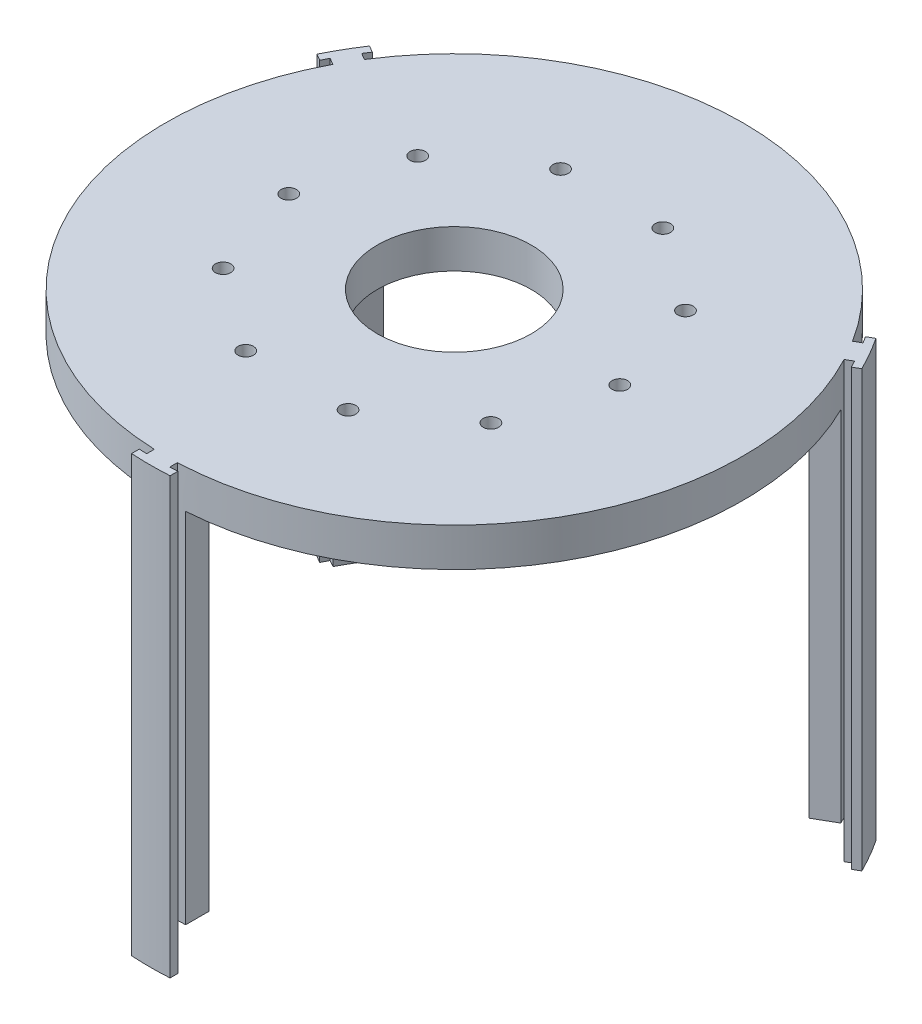
SolidWorks part; units mm, degrees
ref_plane "Front Plane" through (0, 0, 0) normal (0, 0, 1) x (1, 0, 0)
ref_plane "Top Plane" through (0, 0, 0) normal (0, 1, 0) x (1, 0, 0)
ref_plane "Right Plane" through (0, 0, 0) normal (1, 0, 0) x (0, 0, -1)
sketch "Sketch1" plane through (0, 0, 0) normal (0, 1, 0) x (1, 0, 0)
  circle A0 centre (0, 0) radius 37.5
  dimension "D1" = 75
extrude "Boss-Extrude1" add sketch "Sketch1" against normal blind 5
sketch "Sketch2" plane through (0, 0, 0) normal (0, 1, 0) x (1, 0, 0)
  line L0 (-2.75, 0) -> (2.75, 0) construction
  line L1 (0, 39.8902) -> (0, -39.5701) construction
  line L2 (0, -2.75) -> (0, 2.75) construction
  line L4 (-39.7283, 0) -> (39.0263, 0) construction
  circle A0 centre (-21.5, 0) radius 1
  circle A1 centre (-17.3939, 12.6374) radius 1
  circle A2 centre (-6.6439, 20.4477) radius 1
  circle A3 centre (6.6439, 20.4477) radius 1
  circle A4 centre (17.3939, 12.6374) radius 1
  circle A5 centre (21.5, 0) radius 1
  circle A6 centre (17.3939, -12.6374) radius 1
  circle A7 centre (6.6439, -20.4477) radius 1
  circle A8 centre (-6.6439, -20.4477) radius 1
  circle A9 centre (-17.3939, -12.6374) radius 1
  dimension "D1" = 10
  dimension "D2" = 43
extrude "Cut-Extrude1" cut sketch "Sketch2" against normal up to next
sketch "Sketch3" plane through (0, -5, 0) normal (0, -1, 0) x (1, 0, 0)
  line L0 (-2.4705, 37.4185) -> (-2.4705, 34.4146)
  line L1 (-2.4705, 34.4146) -> (2.5295, 34.4146)
  line L2 (2.5295, 34.4146) -> (2.5295, 37.4146)
  line L3 (33.6406, -16.5698) -> (31.0391, -15.0678)
  line L4 (31.0391, -15.0678) -> (28.5391, -19.3979)
  line L5 (28.5391, -19.3979) -> (31.1372, -20.8979)
  line L6 (-31.1702, -20.8488) -> (-28.5687, -19.3468)
  line L7 (-28.5687, -19.3468) -> (-31.0687, -15.0167)
  line L8 (-31.0687, -15.0167) -> (-33.6668, -16.5167)
  arc A0 (2.5295, 37.4146) -> (-2.4705, 37.4185) centre (0, 0) ccw
  arc A1 (31.1372, -20.8979) -> (33.6406, -16.5698) centre (0, 0) ccw
  arc A2 (-33.6668, -16.5167) -> (-31.1702, -20.8488) centre (0, 0) ccw
  dimension "D1" = 3
  dimension "D2" = 3
  dimension "D3" = 5
extrude "Boss-Extrude2" add sketch "Sketch3" along normal blind 46.5
sketch "Sketch4" plane through (0, -5, 0) normal (0, -1, 0) x (1, 0, 0)
  line L0 (-15.5255, 11.28) -> (-15.2841, 13.5767)
  line L1 (-19.1906, 0) -> (-20.3453, 2)
  line L2 (-20.3453, 2) -> (-22.6547, 2)
  line L3 (-22.6547, 2) -> (-23.8094, 0)
  line L4 (-23.8094, 0) -> (-22.6547, -2)
  line L5 (-22.6547, -2) -> (-20.3453, -2)
  line L6 (-20.3453, -2) -> (-19.1906, 0)
  line L7 (-15.2841, 13.5767) -> (-17.1525, 14.9341)
  line L8 (-17.1525, 14.9341) -> (-19.2622, 13.9948)
  line L9 (-19.2622, 13.9948) -> (-19.5036, 11.6981)
  line L10 (-19.5036, 11.6981) -> (-17.6353, 10.3406)
  line L11 (-17.6353, 10.3406) -> (-15.5255, 11.28)
  line L12 (-5.9302, 18.2513) -> (-4.3849, 19.9676)
  line L13 (-4.3849, 19.9676) -> (-5.0986, 22.1639)
  line L14 (-5.0986, 22.1639) -> (-7.3575, 22.6441)
  line L15 (-7.3575, 22.6441) -> (-8.9028, 20.9279)
  line L16 (-8.9028, 20.9279) -> (-8.1892, 18.7315)
  line L17 (-8.1892, 18.7315) -> (-5.9302, 18.2513)
  line L18 (5.9302, 18.2513) -> (8.1892, 18.7315)
  line L19 (8.1892, 18.7315) -> (8.9028, 20.9279)
  line L20 (8.9028, 20.9279) -> (7.3575, 22.6441)
  line L21 (7.3575, 22.6441) -> (5.0986, 22.1639)
  line L22 (5.0986, 22.1639) -> (4.3849, 19.9676)
  line L23 (4.3849, 19.9676) -> (5.9302, 18.2513)
  line L24 (15.5255, 11.28) -> (17.6353, 10.3406)
  line L25 (17.6353, 10.3406) -> (19.5036, 11.6981)
  line L26 (19.5036, 11.6981) -> (19.2622, 13.9948)
  line L27 (19.2622, 13.9948) -> (17.1525, 14.9341)
  line L28 (17.1525, 14.9341) -> (15.2841, 13.5767)
  line L29 (15.2841, 13.5767) -> (15.5255, 11.28)
  line L30 (19.1906, 0) -> (20.3453, -2)
  line L31 (20.3453, -2) -> (22.6547, -2)
  line L32 (22.6547, -2) -> (23.8094, 0)
  line L33 (23.8094, 0) -> (22.6547, 2)
  line L34 (22.6547, 2) -> (20.3453, 2)
  line L35 (20.3453, 2) -> (19.1906, 0)
  line L36 (15.5255, -11.28) -> (15.2841, -13.5767)
  line L37 (15.2841, -13.5767) -> (17.1525, -14.9341)
  line L38 (17.1525, -14.9341) -> (19.2622, -13.9948)
  line L39 (19.2622, -13.9948) -> (19.5036, -11.6981)
  line L40 (19.5036, -11.6981) -> (17.6353, -10.3406)
  line L41 (17.6353, -10.3406) -> (15.5255, -11.28)
  line L42 (5.9302, -18.2513) -> (4.3849, -19.9676)
  line L43 (4.3849, -19.9676) -> (5.0986, -22.1639)
  line L44 (5.0986, -22.1639) -> (7.3575, -22.6441)
  line L45 (7.3575, -22.6441) -> (8.9028, -20.9279)
  line L46 (8.9028, -20.9279) -> (8.1892, -18.7315)
  line L47 (8.1892, -18.7315) -> (5.9302, -18.2513)
  line L48 (-5.9302, -18.2513) -> (-8.1892, -18.7315)
  line L49 (-8.1892, -18.7315) -> (-8.9028, -20.9279)
  line L50 (-8.9028, -20.9279) -> (-7.3575, -22.6441)
  line L51 (-7.3575, -22.6441) -> (-5.0986, -22.1639)
  line L52 (-5.0986, -22.1639) -> (-4.3849, -19.9676)
  line L53 (-4.3849, -19.9676) -> (-5.9302, -18.2513)
  line L54 (-15.5255, -11.28) -> (-17.6353, -10.3406)
  line L55 (-17.6353, -10.3406) -> (-19.5036, -11.6981)
  line L56 (-19.5036, -11.6981) -> (-19.2622, -13.9948)
  line L57 (-19.2622, -13.9948) -> (-17.1525, -14.9341)
  line L58 (-17.1525, -14.9341) -> (-15.2841, -13.5767)
  line L59 (-15.2841, -13.5767) -> (-15.5255, -11.28)
  circle A0 centre (-21.5, 0) radius 2 construction
  dimension "D1" = 10
extrude "Cut-Extrude2" cut sketch "Sketch4" against normal blind 1.6
sketch "Sketch5" plane through (0, 0, 0) normal (0, 1, 0) x (1, 0, 0)
  line L0 (-2.4982, -38.4161) -> (-2.4982, -39.4209)
  line L1 (2.5018, -38.4158) -> (2.5018, -39.4207)
  line L2 (1.5018, -38.4679) -> (1.5018, -37.4699)
  line L3 (-1.4982, -38.468) -> (-1.4982, -37.4701)
  line L4 (-32.0202, 21.3715) -> (-32.8904, 21.8739)
  line L5 (-34.52, 17.0413) -> (-35.3902, 17.5437)
  line L6 (-34.0651, 17.9333) -> (-33.2008, 17.4343)
  line L7 (-32.5652, 20.5315) -> (-31.7009, 20.0325)
  line L8 (34.5184, 17.0446) -> (35.3886, 17.547)
  line L9 (32.0182, 21.3746) -> (32.8884, 21.877)
  line L10 (32.5633, 20.5346) -> (31.699, 20.0356)
  line L11 (34.0634, 17.9366) -> (33.1991, 17.4376)
  arc A0 (-2.4982, -39.4209) -> (2.5018, -39.4207) centre (0, 0) ccw
  arc A1 (-1.4982, -37.4701) -> (1.5018, -37.4699) centre (0, 0) ccw
  arc A2 (2.5018, -38.4158) -> (1.5018, -38.4679) centre (0, 0) cw
  arc A3 (-2.4982, -38.4161) -> (-1.4982, -38.468) centre (0, 0) ccw
  arc A4 (-32.8904, 21.8739) -> (-35.3902, 17.5437) centre (0, 0) ccw
  arc A5 (-31.7009, 20.0325) -> (-33.2008, 17.4343) centre (0, 0) ccw
  arc A6 (-34.52, 17.0413) -> (-34.0651, 17.9333) centre (0, 0) cw
  arc A7 (-32.0202, 21.3715) -> (-32.5652, 20.5315) centre (0, 0) ccw
  arc A8 (35.3886, 17.547) -> (32.8884, 21.877) centre (0, 0) ccw
  arc A9 (33.1991, 17.4376) -> (31.699, 20.0356) centre (0, 0) ccw
  arc A10 (32.0182, 21.3746) -> (32.5633, 20.5346) centre (0, 0) cw
  arc A11 (34.5184, 17.0446) -> (34.0634, 17.9366) centre (0, 0) ccw
  circle A12 centre (0, 0) radius 37.5 construction
  dimension "D1" = 3
  dimension "D2" = 5
  dimension "D3" = 2
  dimension "D4" = 1.0049
  dimension "D5" = 1
extrude "Boss-Extrude3" add sketch "Sketch5" against normal blind 56.5
sketch "Sketch6" plane through (0, 0, 0) normal (0, 1, 0) x (1, 0, 0)
  circle A0 centre (0, 0) radius 10
extrude "Cut-Extrude3" cut sketch "Sketch6" against normal up to next
